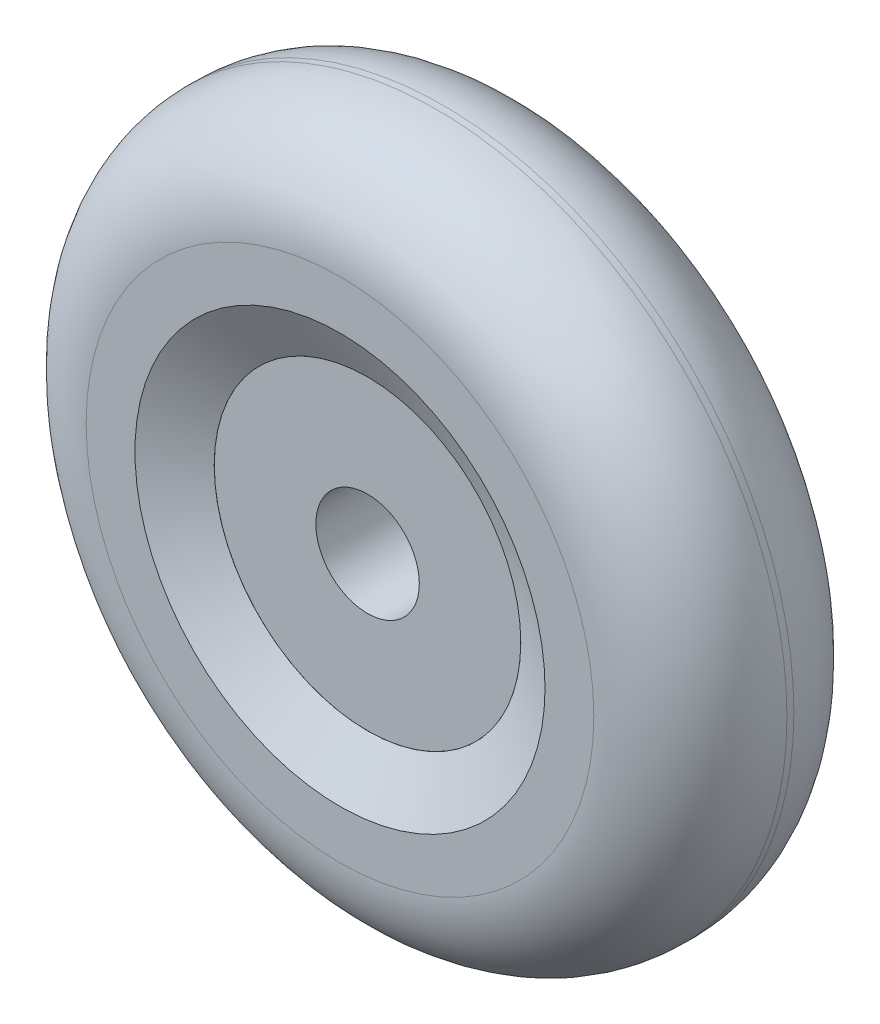
SolidWorks part; units mm, degrees
ref_plane "Front Plane" through (0, 0, 0) normal (0, 0, 1) x (1, 0, 0)
ref_plane "Top Plane" through (0, 0, 0) normal (0, 1, 0) x (1, 0, 0)
ref_plane "Right Plane" through (0, 0, 0) normal (1, 0, 0) x (0, 0, -1)
other "Centro de masa"
sketch "Croquis1" plane through (0, 0, 0) normal (0, 0, 1) x (1, 0, 0)
  circle A0 centre (0, 0) radius 7.9375
  circle A1 centre (0, 0) radius 101.6
  dimension "D1" = 203.2
  dimension "D2" = 15.875
extrude "Saliente-Extruir1" add sketch "Croquis1" along normal mid plane 58
fillet "Redondeo1" radius 28 2 edges at (101.6, 0, 29) (101.6, 0, -29)
sketch "Croquis2" plane through (0, 0, -29) normal (0, 0, -1) x (-1, 0, 0)
  circle A0 centre (0, 0) radius 44.45
  dimension "D1" = 88.9
extrude "Cortar-Extruir1" cut sketch "Croquis2" against normal blind 8
mirror "Simetría3" about plane through (0, 0, 0) normal (0, 0, 1) of "Cortar-Extruir1"
chamfer "Chaflán1" distance 15 angle 28 1 edges at (-44.45, 0, -29) first distance on face at (-44.45, 0, -29)
chamfer "Chaflán2" distance 15 angle 28 1 edges at (-44.45, 0, 29) first distance on face at (-44.45, 0, 21)
sketch "Croquis3" plane through (0, 0, 0) normal (1, 0, 0) x (0, 0, -1)
  line L0 (0, -121.3315) -> (0, 121.3315)
extrude "Cortar-Extruir2" cut sketch "Croquis3" against normal through all and the other way through all
mirror "Simetría4" about plane through (376.3755, -121.3315, 0) normal (0, 0, 1) of bodies 104
sketch "Croquis5" plane through (0, 0, 21) normal (0, 0, 1) x (1, 0, 0)
  circle A0 centre (0, 0) radius 7.9375 construction
  circle A1 centre (0, 0) radius 7.9375
extrude "Saliente-Extruir2" add sketch "Croquis5" against normal blind 120 separate body
sketch "Croquis6" plane through (0, 0, -99) normal (0, 0, -1) x (-1, 0, 0)
  circle A0 centre (0, 0) radius 12.9375
  circle A1 centre (0, 0) radius 7.9375 construction
  circle A2 centre (0, 0) radius 7.9375
  dimension "D1" = 5
extrude "Saliente-Extruir3" add sketch "Croquis6" against normal blind 20 separate body
sketch "Croquis8" plane through (0, 0, 0) normal (0, 1, 0) x (1, 0, 0)
  line L0 (0, 99) -> (0, 79) construction
  line L1 (12.9375, 99) -> (-12.9375, 99) construction
  line L2 (-12.9375, 79) -> (12.9375, 79) construction
  circle A0 centre (0, 89) radius 3
  dimension "D1" = 6
extrude "Cortar-Extruir3" cut sketch "Croquis8" along normal blind 20
sketch "Croquis10" plane through (0, 0, -99) normal (0, 0, -1) x (-1, 0, 0)
  line L0 (0, 0) -> (0, 17.5) construction
  line L1 (-5, 17.5) -> (5, 17.5)
  line L2 (12.6554, 13.0801) -> (17.6554, 4.4199)
  line L3 (17.6554, -4.4199) -> (12.6554, -13.0801)
  line L4 (5, -17.5) -> (-5, -17.5)
  line L5 (-12.6554, -13.0801) -> (-17.6554, -4.4199)
  line L6 (-17.6554, 4.4199) -> (-12.6554, 13.0801)
  line L7 (-15.1554, 8.75) -> (15.1554, -8.75) construction
  line L8 (-15.1554, -8.75) -> (15.1554, 8.75) construction
  line L9 (0, 0) -> (0, -17.5) construction
  circle A0 centre (0, 0) radius 7.9375 construction
  circle A1 centre (0, 0) radius 17.5 construction
  circle A2 centre (0, 0) radius 7.9375
  arc A3 (5, 17.5) -> (12.6554, 13.0801) centre (10.8566, 18.8041) ccw
  arc A4 (17.6554, 4.4199) -> (17.6554, -4.4199) centre (21.7131, 0) ccw
  arc A5 (12.6554, -13.0801) -> (5, -17.5) centre (10.8566, -18.8041) ccw
  arc A6 (-5, -17.5) -> (-12.6554, -13.0801) centre (-10.8566, -18.8041) ccw
  arc A7 (-17.6554, -4.4199) -> (-17.6554, 4.4199) centre (-21.7131, 0) ccw
  arc A8 (-12.6554, 13.0801) -> (-5, 17.5) centre (-10.8566, 18.8041) ccw
  point P20 (0, 0)
  point P41 (0, 0)
  dimension "D2" = 35
  dimension "D4" = 6
  dimension "D1" = 10
  dimension "D3" = 6
  dimension "D5" = 6
extrude "Saliente-Extruir4" add sketch "Croquis10" along normal blind 10 contours L1 A3 L2 A4 L3 A5 L4 A6 L5 A7 L6 A8
fillet "Redondeo2" radius 1 12 edges at (5, -17.5, -104) (12.6554, -13.0801, -104) (17.6554, -4.4199, -104) (17.6554, 4.4199, -104) (12.6554, 13.0801, -104) (5, 17.5, -104) (-5, -17.5, -104) (-12.6554, -13.0801, -104) (-17.6554, 4.4199, -104) (-17.6554, -4.4199, -104) (-12.6554, 13.0801, -104) (-5, 17.5, -104)
sketch "Croquis11" plane through (0, 0, 21) normal (0, 0, 1) x (1, 0, 0)
  circle A0 centre (0, 0) radius 15
  dimension "D1" = 30
extrude "Cortar-Extruir4" cut sketch "Croquis11" against normal blind 50
sketch "Croquis12" plane through (0, 0, 21) normal (0, 0, 1) x (1, 0, 0)
  circle A0 centre (0, 0) radius 15 construction
  circle A1 centre (0, 0) radius 15
  circle A2 centre (0, 0) radius 7.9375 construction
  circle A3 centre (0, 0) radius 7.9375
extrude "Saliente-Extruir5" add sketch "Croquis12" against normal blind 50 and the other way blind 5 separate body
sketch "Croquis13" plane through (0, 0, 26) normal (0, 0, 1) x (1, 0, 0)
  line L0 (0, -25) -> (0, 25) construction
  line L1 (5, -25) -> (5, -6.1647)
  line L2 (-5, -25) -> (-5, -6.1647)
  line L3 (-5, 25) -> (5, 25)
  line L4 (-5, -25) -> (5, -25)
  line L5 (-25, 0) -> (25, 0) construction
  line L6 (-25, -5) -> (-6.1647, -5)
  line L7 (-25, 5) -> (-6.1647, 5)
  line L8 (-25, 5) -> (-25, 0)
  line L9 (-25, 0) -> (-25, -5)
  line L10 (25, -5) -> (25, 5)
  line L11 (6.1647, 5) -> (25, 5)
  line L12 (-25, 5) -> (25, 5) construction
  line L13 (5, 6.1647) -> (5, 25)
  line L14 (5, -25) -> (5, 25) construction
  line L15 (6.1647, -5) -> (25, -5)
  line L16 (-25, -5) -> (25, -5) construction
  line L17 (-5, 6.1647) -> (-5, 25)
  line L18 (-5, -25) -> (-5, 25) construction
  arc A1 (5, 6.1647) -> (-5, 6.1647) centre (0, 0) ccw
  arc A2 (6.1647, -5) -> (6.1647, 5) centre (0, 0) ccw
  arc A3 (-5, -6.1647) -> (5, -6.1647) centre (0, 0) ccw
  circle A4 centre (0, 18.5) radius 3
  circle A5 centre (0, 0) radius 7.9375 construction
  arc A6 (-6.1647, 5) -> (-6.1647, -5) centre (0, 0) ccw
  circle A7 centre (18.5, 0) radius 3
  circle A8 centre (0, -18.5) radius 3
  circle A9 centre (-18.5, 0) radius 3
  point P34 (0, 0)
  dimension "D7" = 6
  dimension "D1" = 50
  dimension "D6" = 18.5
  dimension "D2" = 5
  dimension "D3" = 5
  dimension "D4" = 5
  dimension "D5" = 5
  dimension "D8" = 4
sketch "Croquis15" plane through (0, 0, 21) normal (0, 0, 1) x (1, 0, 0)
  circle A1 centre (0, 0) radius 7.9375
  circle A2 centre (0, 0) radius 7.9375
  dimension "D1" = 0
extrude "Saliente-Extruir7" add sketch "Croquis15" along normal up to surface (5 mm away) separate body up to face at (15, 0, 26)
combine bodies "Combinar1" operation type add bodies to combine 113 106
extrude "Saliente-Extruir8" add sketch "Croquis13" against normal up to surface (5 mm away) separate body up to face at (15, 0, 21)
combine bodies "Combinar2" operation type add bodies to combine 111 116 118 115 117
sketch "Croquis17" plane through (0, 0, 0) normal (0, 1, 0) x (1, 0, 0)
  line L0 (0, 0) -> (0, 29) construction
  line L1 (15, 29) -> (-15, 29) construction
  circle A0 centre (0, 24) radius 3
  dimension "D1" = 6
  dimension "D2" = 5
extrude "Cortar-Extruir5" cut sketch "Croquis17" along normal blind 16
delete or keep bodies "Sólido-Eliminar/Conservar 1" type delete bodies bodies 120 109 114
